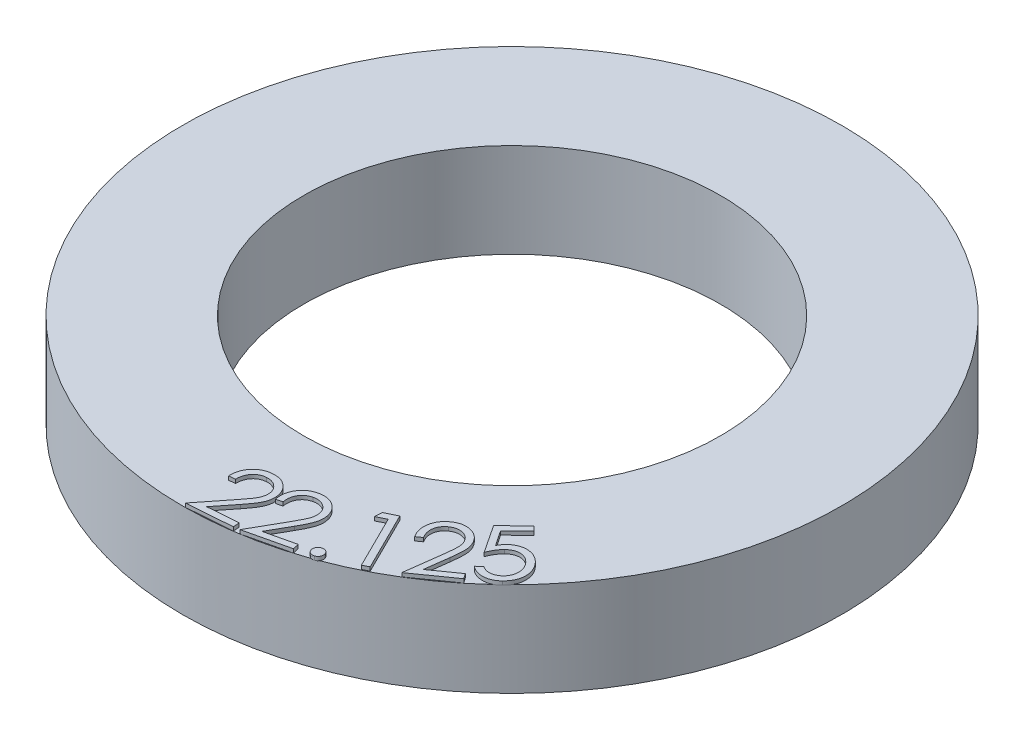
SolidWorks part; units mm, degrees
ref_plane "Front Plane" through (0, 0, 0) normal (0, 0, 1) x (1, 0, 0)
ref_plane "Top Plane" through (0, 0, 0) normal (0, 1, 0) x (1, 0, 0)
ref_plane "Right Plane" through (0, 0, 0) normal (1, 0, 0) x (0, 0, -1)
ref_axis "X" through (-88.99, 0, 0) along (1, 0, 0)
ref_axis "Y" through (0, 55, 0) along (0, -1, 0)
ref_axis "Z" through (0, 0, -88.99) along (0, 0, 1)
sketch "Sketch1" plane through (0, 0, 0) normal (0, 1, 0) x (1, 0, 0)
  circle A0 centre (0, 0) radius 17.5
  circle A1 centre (0, 0) radius 11.0625
  dimension "D1" = 35
  dimension "D2" = 22.125
extrude "Boss-Extrude1" add sketch "Sketch1" along normal blind 5
sketch "Sketch6" plane through (0, 5, 0) normal (0, 1, 0) x (1, 0, 0)
  text T0 "22.125"
extrude "Boss-Extrude6" add sketch "Sketch6" along normal blind 0.2
